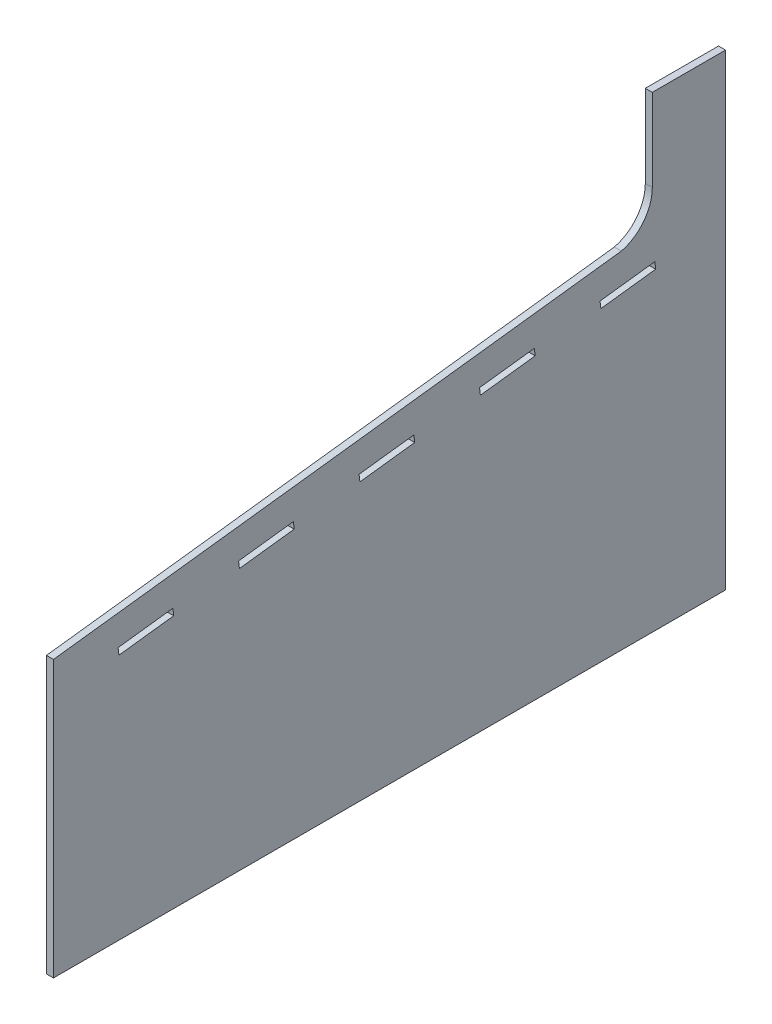
SolidWorks part; units mm, degrees
material "Beech"
ref_plane "Front Plane" through (0, 0, 0) normal (0, 0, 1) x (1, 0, 0)
ref_plane "Top Plane" through (0, 0, 0) normal (0, 1, 0) x (1, 0, 0)
ref_plane "Right Plane" through (0, 0, 0) normal (1, 0, 0) x (0, 0, -1)
sketch "Sketch1" plane through (0, 0, 0) normal (1, 0, 0) x (0, 0, -1)
  line L0 (0, 250) -> (514.5695, 313.1812)
  line L1 (0, 0) -> (609, 0)
  line L2 (0, 0) -> (0, 250)
  line L4 (609, 0) -> (609, 250)
  line L6 (609, 250) -> (609, 423.72)
  line L7 (609, 423.72) -> (542.65, 423.72)
  line L8 (542.65, 349.09) -> (542.65, 423.72)
  line L9 (0, 250) -> (609, 250) construction
  line L10 (514.5695, 313.1812) -> (609, 324.7758) construction
  arc A0 (514.5695, 313.1812) -> (542.65, 349.09) centre (505.65, 349.09) ccw
  point P10 (549, 348.7479)
  point P12 (549, 348.7479)
  point P13 (549, 348.7479)
  point P14 (549, 350.0864)
  dimension "D4" = 37
  dimension "D1" = 609
  dimension "D2" = 250
  dimension "D3" = 66.35
  dimension "D5" = 7
  dimension "D6" = 173.72
  dimension "D7" = 74.63
extrude "Boss-Extrude1" add sketch "Sketch1" along normal blind 6.35
sketch "Sketch2" plane through (6.35, 0, 0) normal (1, 0, 0) x (0, 0, -1)
  line L0 (514.5695, 313.1812) -> (609, 324.7758) construction
  line L1 (609, 0) -> (609, 423.72) construction
  line L2 (514.5695, 313.1812) -> (0, 250) construction
  line L3 (0, 222.7972) -> (609, 297.573) construction
  line L4 (0, 250) -> (0, 0) construction
  line L5 (58.5602, 229.9875) -> (59.3341, 223.6849)
  line L6 (59.3341, 223.6849) -> (108.9614, 229.7783)
  line L7 (108.9614, 229.7783) -> (108.1875, 236.081)
  line L8 (108.1875, 236.081) -> (58.5602, 229.9875)
  line L9 (217.3676, 249.4866) -> (167.7403, 243.3932)
  line L10 (167.7403, 243.3932) -> (168.5142, 237.0905)
  line L11 (168.5142, 237.0905) -> (218.1415, 243.184)
  line L12 (218.1415, 243.184) -> (217.3676, 249.4866)
  line L13 (326.5477, 262.8922) -> (276.9204, 256.7988)
  line L14 (276.9204, 256.7988) -> (277.6942, 250.4961)
  line L15 (277.6942, 250.4961) -> (327.3216, 256.5896)
  line L16 (327.3216, 256.5896) -> (326.5477, 262.8922)
  line L17 (435.7278, 276.2979) -> (386.1005, 270.2044)
  line L18 (386.1005, 270.2044) -> (386.8743, 263.9017)
  line L19 (386.8743, 263.9017) -> (436.5016, 269.9952)
  line L20 (436.5016, 269.9952) -> (435.7278, 276.2979)
  line L21 (544.9078, 289.7035) -> (495.2805, 283.61)
  line L22 (495.2805, 283.61) -> (496.0544, 277.3074)
  line L23 (496.0544, 277.3074) -> (545.6817, 283.4008)
  line L24 (545.6817, 283.4008) -> (544.9078, 289.7035)
  dimension "D1" = 27
  dimension "D2" = 50
  dimension "D3" = 6.35
  dimension "D4" = 59
extrude "Cut-Extrude1" cut sketch "Sketch2" against normal blind 6.35
